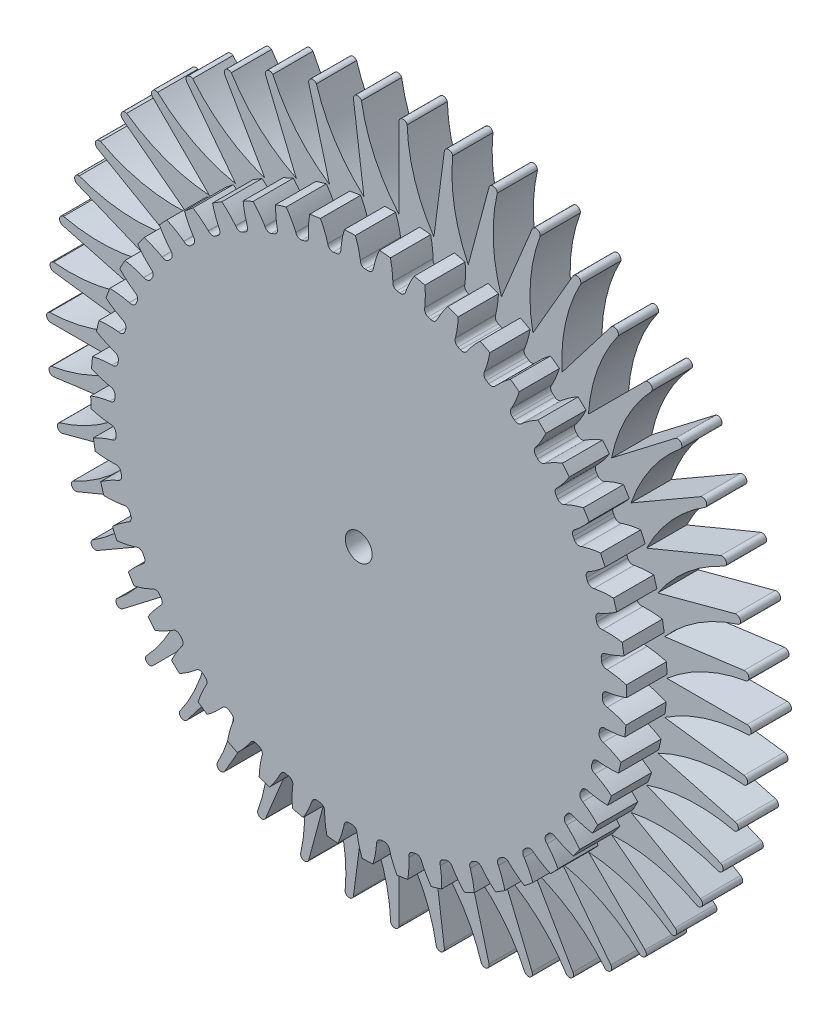
SolidWorks part; units mm, degrees
ref_plane "Front" through (0, 0, 0) normal (0, 0, 1) x (1, 0, 0)
ref_plane "Top" through (0, 0, 0) normal (0, 1, 0) x (1, 0, 0)
ref_plane "Right" through (0, 0, 0) normal (1, 0, 0) x (0, 0, -1)
sketch "Sketch1" plane through (0, 0, 0) normal (0, 0, 1) x (1, 0, 0)
  line L0 (-609.6, 0) -> (609.6, 0) construction
  circle A0 centre (0, 0) radius 31.75
  circle A1 centre (0, 0) radius 30.48 construction
  circle A3 centre (0, 0) radius 28.8925 construction
  dimension "D3" = 1.27
  dimension "D1" = 2.8575
extrude "Boss-Extrude1" add sketch "Sketch1" against normal blind 4.7625
sketch "Sketch3" plane through (0, 0, 0) normal (0, 0, 1) x (1, 0, 0)
  line L0 (0, 0) -> (0, 31.75) construction
  line L1 (-7.3885, 28.5692) -> (0, 30.48)
  line L2 (-9.5921, 30.48) -> (9.5921, 30.48) construction
  line L3 (-9.2865, 28.0783) -> (9.2865, 32.8817) construction
  line L4 (-7.3885, 28.5692) -> (0, 0) construction
  line L5 (-18.8456, 22.7076) -> (0, 0) construction
  line L6 (-18.8456, 22.7076) -> (-3.0091, 35.8506) construction
  line L7 (-5.1519, 29.0559) -> (0, 0) construction
  line L8 (-5.1519, 29.0559) -> (0.1081, 29.9886) construction
  arc A0 (-7.3885, 28.5692) -> (-18.8456, 22.7076) centre (0, 0) ccw
  circle A1 centre (0, 0) radius 30.48 construction
  circle A2 centre (0, 0) radius 29.5091 construction
  arc A3 (-7.3885, 28.5692) -> (-5.1519, 29.0559) centre (0, 0) cw
  circle A4 centre (0, 0) radius 31.75 construction
  point P6 (0, 30.48)
  dimension "D1" = 7.6316
  dimension "Pressure Angle" = 14.5
  dimension "D2" = 12.9737
  dimension "D3" = 20.5799
  dimension "D4" = 2.2895
  dimension "D5" = 5.3421
sketch "Sketch4" plane through (0, 0, 0) normal (0, 0, 1) x (1, 0, 0)
  line L0 (0, 0) -> (0.9967, 30.4474) construction
  line L1 (0.192, 29.5085) -> (0.192, 28.8919)
  line L2 (0, 30.48) -> (1.9935, 30.4147) construction
  line L3 (1.7384, 29.4579) -> (1.698, 28.8426)
  line L4 (0.192, 28.8919) -> (0, 0) construction
  line L5 (0, 0) -> (0, 31.75) construction
  line L6 (-18.8456, 22.7076) -> (-3.0091, 35.8506) construction
  line L7 (-18.8456, 22.7076) -> (-3.0091, 35.8506) construction
  arc A0 (1.698, 28.8426) -> (0.192, 28.8919) centre (0, 0) ccw
  arc A1 (0, 30.48) -> (1.9935, 30.4147) centre (0, 0) cw construction
  circle A2 centre (0, 0) radius 30.48 construction
  circle A3 centre (0, 0) radius 29.5091 construction
  circle A4 centre (0, 0) radius 28.8925 construction
  arc A5 (5.3474, 35.577) -> (-3.0091, 35.8506) centre (0, 0) ccw
  spline S0 degree 2 poles (-3.0091, 35.8506) (-0.3489, 33.0435) (0.192, 29.5085) knots 0 0 0 1 1 1
  spline S1 degree 2 poles (5.3474, 35.577) (2.5093, 32.95) (1.7384, 29.4579) knots 0 0 0 1 1 1
  dimension "D1" = 1.9949
extrude "Cut-Extrude1" cut sketch "Sketch4" against normal through all
fillet "Fillet1" radius 0.5985 2 edges at (1.698, 28.8426, -2.3813) (0.192, 28.8919, -2.3813)
pattern_circular "CirPattern1" count 48 over 360 about axis through (0, 0, -4.7625) along (0, 0, 1) of "Cut-Extrude1", "Fillet1"
sketch "Sketch5" plane through (0, 0, 0) normal (0, 0, 1) x (1, 0, 0)
  line L0 (0, 2.7788) -> (0, 0) construction
  line L1 (-1.1906, 1.05) -> (1.1906, 1.05) construction
  line L2 (-1.1906, 1.05) -> (-1.1906, 2.7788) construction
  line L3 (-1.1906, 2.7788) -> (1.1906, 2.7788) construction
  line L4 (1.1906, 1.05) -> (1.1906, 2.7788) construction
  line L5 (-1.1906, 1.05) -> (1.1906, 2.7788) construction
  line L6 (-1.1906, 2.7788) -> (1.1906, 1.05) construction
  circle A0 centre (0, 0) radius 1.5875
  point P3 (0, 1.9144)
  point P8 (0, 1.5875)
  point P9 (0, -1.5875)
  dimension "Bore Min" = 3.175
  dimension "Keyway Wd" = 2.3813
  dimension "Keyway Dpt." = 1.1913
extrude "Cut-Extrude2" cut sketch "Sketch5" against normal through all
sketch "Pitch Dia" plane through (0, 0, 0) normal (0, 0, 1) x (1, 0, 0)
  circle A0 centre (0, 0) radius 30.48 construction
  circle A1 centre (0, 0) radius 30.48 construction
sketch "Sketch6" plane through (0, 0, -4.7625) normal (0, 0, -1) x (-1, 0, 0)
  line L0 (8.2175, 30.6681) -> (10.6742, 39.8367)
  line L98 (12.1502, 29.3332) -> (15.7826, 38.1026)
  line L195 (4.1442, 31.4784) -> (5.3832, 40.8892)
  line L196 (15.875, 27.4963) -> (20.621, 35.7166)
  line L291 (0, 0) -> (0, 1.5875)
  line L292 (19.3282, 25.189) -> (25.1065, 32.7195)
  line L293 (22.4506, 22.4506) -> (29.1625, 29.1625)
  line L294 (25.189, 19.3282) -> (32.7195, 25.1065)
  line L295 (27.4963, 15.875) -> (35.7166, 20.621)
  line L296 (29.3332, 12.1502) -> (38.1026, 15.7826)
  line L297 (30.6681, 8.2175) -> (39.8367, 10.6742)
  line L298 (31.4784, 4.1442) -> (40.8892, 5.3832)
  line L299 (31.75, 0) -> (41.242, 0)
  line L300 (31.4784, -4.1442) -> (40.8892, -5.3832)
  line L301 (30.6681, -8.2175) -> (39.8367, -10.6742)
  line L302 (29.3332, -12.1502) -> (38.1026, -15.7826)
  line L303 (27.4963, -15.875) -> (35.7166, -20.621)
  line L304 (25.189, -19.3282) -> (32.7195, -25.1065)
  line L305 (22.4506, -22.4506) -> (29.1625, -29.1625)
  line L306 (19.3282, -25.189) -> (25.1065, -32.7195)
  line L307 (15.875, -27.4963) -> (20.621, -35.7166)
  line L308 (12.1502, -29.3332) -> (15.7826, -38.1026)
  line L309 (8.2175, -30.6681) -> (10.6742, -39.8367)
  line L310 (4.1442, -31.4784) -> (5.3832, -40.8892)
  line L311 (0, -31.75) -> (0, -41.242)
  line L312 (-4.1442, -31.4784) -> (-5.3832, -40.8892)
  line L313 (-8.2175, -30.6681) -> (-10.6742, -39.8367)
  line L314 (-12.1502, -29.3332) -> (-15.7826, -38.1026)
  line L315 (-15.875, -27.4963) -> (-20.621, -35.7166)
  line L316 (-19.3282, -25.189) -> (-25.1065, -32.7195)
  line L317 (-22.4506, -22.4506) -> (-29.1625, -29.1625)
  line L318 (-25.189, -19.3282) -> (-32.7195, -25.1065)
  line L319 (-27.4963, -15.875) -> (-35.7166, -20.621)
  line L320 (-29.3332, -12.1502) -> (-38.1026, -15.7826)
  line L321 (-30.6681, -8.2175) -> (-39.8367, -10.6742)
  line L322 (-31.4784, -4.1442) -> (-40.8892, -5.3832)
  line L323 (-31.75, 0) -> (-41.242, 0)
  line L324 (-31.4784, 4.1442) -> (-40.8892, 5.3832)
  line L325 (-30.6681, 8.2175) -> (-39.8367, 10.6742)
  line L326 (-29.3332, 12.1502) -> (-38.1026, 15.7826)
  line L327 (-27.4963, 15.875) -> (-35.7166, 20.621)
  line L328 (-25.189, 19.3282) -> (-32.7195, 25.1065)
  line L329 (-22.4506, 22.4506) -> (-29.1625, 29.1625)
  line L330 (-19.3282, 25.189) -> (-25.1065, 32.7195)
  line L331 (-15.875, 27.4963) -> (-20.621, 35.7166)
  line L332 (-12.1502, 29.3332) -> (-15.7826, 38.1026)
  line L333 (-8.2175, 30.6681) -> (-10.6742, 39.8367)
  line L334 (-4.1442, 31.4784) -> (-5.3832, 40.8892)
  line L335 (0, 31.75) -> (0, 41.242)
  arc A98 (5.3832, 40.8892) -> (4.4351, 41.1675) centre (4.8874, 40.9544) ccw
  circle A146 centre (0, 0) radius 1.5875
  arc A147 (0, 31.75) -> (4.4351, 41.1675) centre (-14.4043, 44.2867) ccw
  arc A148 (10.6742, 39.8367) -> (9.7706, 40.2364) centre (10.1913, 39.9661) ccw
  arc A149 (4.1442, 31.4784) -> (9.7706, 40.2364) centre (-8.5005, 45.7879) ccw
  arc A150 (15.7826, 38.1026) -> (14.9389, 38.6168) centre (15.3207, 38.294) ccw
  arc A151 (8.2175, 30.6681) -> (14.9389, 38.6168) centre (-2.4513, 46.5058) ccw
  arc A152 (20.621, 35.7166) -> (19.8516, 36.3365) centre (20.188, 35.9666) ccw
  arc A153 (12.1502, 29.3332) -> (19.8516, 36.3365) centre (3.6399, 46.4278) ccw
  arc A154 (25.1065, 32.7195) -> (24.4246, 33.4345) centre (24.7099, 33.0239) ccw
  arc A155 (15.875, 27.4963) -> (24.4246, 33.4345) centre (9.6688, 45.5555) ccw
  arc A156 (29.1625, 29.1625) -> (28.5798, 29.9604) centre (28.8089, 29.5161) ccw
  arc A157 (19.3282, 25.189) -> (28.5798, 29.9604) centre (15.5323, 43.9038) ccw
  arc A158 (32.7195, 25.1065) -> (32.2459, 25.9737) centre (32.4151, 25.5032) ccw
  arc A159 (22.4506, 22.4506) -> (32.2459, 25.9737) centre (21.13, 41.5008) ccw
  arc A160 (35.7166, 20.621) -> (35.3603, 21.5426) centre (35.4666, 21.054) ccw
  arc A161 (25.189, 19.3282) -> (35.3603, 21.5426) centre (26.3662, 38.3877) ccw
  arc A162 (38.1026, 15.7826) -> (37.8696, 16.7428) centre (37.9113, 16.2446) ccw
  arc A163 (27.4963, 15.875) -> (37.8696, 16.7428) centre (31.1512, 34.6178) ccw
  arc A164 (39.8367, 10.6742) -> (39.731, 11.6566) centre (39.7073, 11.1572) ccw
  arc A165 (29.3332, 12.1502) -> (39.731, 11.6566) centre (35.4033, 30.2556) ccw
  arc A166 (40.8892, 5.3832) -> (40.9126, 6.371) centre (40.8239, 5.8789) ccw
  arc A167 (30.6681, 8.2175) -> (40.9126, 6.371) centre (39.0495, 25.3757) ccw
  arc A168 (41.242, 0) -> (41.3942, 0.9763) centre (41.242, 0.5) ccw
  arc A169 (31.4784, 4.1442) -> (41.3942, 0.9763) centre (42.0277, 20.0616) ccw
  arc A170 (40.8892, -5.3832) -> (41.1675, -4.4351) centre (40.9544, -4.8874) ccw
  arc A171 (31.75, 0) -> (41.1675, -4.4351) centre (44.2867, 14.4043) ccw
  arc A172 (39.8367, -10.6742) -> (40.2364, -9.7706) centre (39.9661, -10.1913) ccw
  arc A173 (31.4784, -4.1442) -> (40.2364, -9.7706) centre (45.7879, 8.5005) ccw
  arc A174 (38.1026, -15.7826) -> (38.6168, -14.9389) centre (38.294, -15.3207) ccw
  arc A175 (30.6681, -8.2175) -> (38.6168, -14.9389) centre (46.5058, 2.4513) ccw
  arc A176 (35.7166, -20.621) -> (36.3365, -19.8516) centre (35.9666, -20.188) ccw
  arc A177 (29.3332, -12.1502) -> (36.3365, -19.8516) centre (46.4278, -3.6399) ccw
  arc A178 (32.7195, -25.1065) -> (33.4345, -24.4246) centre (33.0239, -24.7099) ccw
  arc A179 (27.4963, -15.875) -> (33.4345, -24.4246) centre (45.5555, -9.6688) ccw
  arc A180 (29.1625, -29.1625) -> (29.9604, -28.5798) centre (29.5161, -28.8089) ccw
  arc A181 (25.189, -19.3282) -> (29.9604, -28.5798) centre (43.9038, -15.5323) ccw
  arc A182 (25.1065, -32.7195) -> (25.9737, -32.2459) centre (25.5032, -32.4151) ccw
  arc A183 (22.4506, -22.4506) -> (25.9737, -32.2459) centre (41.5008, -21.13) ccw
  arc A184 (20.621, -35.7166) -> (21.5426, -35.3603) centre (21.054, -35.4666) ccw
  arc A185 (19.3282, -25.189) -> (21.5426, -35.3603) centre (38.3877, -26.3662) ccw
  arc A186 (15.7826, -38.1026) -> (16.7428, -37.8696) centre (16.2446, -37.9113) ccw
  arc A187 (15.875, -27.4963) -> (16.7428, -37.8696) centre (34.6178, -31.1512) ccw
  arc A188 (10.6742, -39.8367) -> (11.6566, -39.731) centre (11.1572, -39.7073) ccw
  arc A189 (12.1502, -29.3332) -> (11.6566, -39.731) centre (30.2556, -35.4033) ccw
  arc A190 (5.3832, -40.8892) -> (6.371, -40.9126) centre (5.8789, -40.8239) ccw
  arc A191 (8.2175, -30.6681) -> (6.371, -40.9126) centre (25.3757, -39.0495) ccw
  arc A192 (0, -41.242) -> (0.9763, -41.3942) centre (0.5, -41.242) ccw
  arc A193 (4.1442, -31.4784) -> (0.9763, -41.3942) centre (20.0616, -42.0277) ccw
  arc A194 (-5.3832, -40.8892) -> (-4.4351, -41.1675) centre (-4.8874, -40.9544) ccw
  arc A195 (0, -31.75) -> (-4.4351, -41.1675) centre (14.4043, -44.2867) ccw
  arc A196 (-10.6742, -39.8367) -> (-9.7706, -40.2364) centre (-10.1913, -39.9661) ccw
  arc A197 (-4.1442, -31.4784) -> (-9.7706, -40.2364) centre (8.5005, -45.7879) ccw
  arc A198 (-15.7826, -38.1026) -> (-14.9389, -38.6168) centre (-15.3207, -38.294) ccw
  arc A199 (-8.2175, -30.6681) -> (-14.9389, -38.6168) centre (2.4513, -46.5058) ccw
  arc A200 (-20.621, -35.7166) -> (-19.8516, -36.3365) centre (-20.188, -35.9666) ccw
  arc A201 (-12.1502, -29.3332) -> (-19.8516, -36.3365) centre (-3.6399, -46.4278) ccw
  arc A202 (-25.1065, -32.7195) -> (-24.4246, -33.4345) centre (-24.7099, -33.0239) ccw
  arc A203 (-15.875, -27.4963) -> (-24.4246, -33.4345) centre (-9.6688, -45.5555) ccw
  arc A204 (-29.1625, -29.1625) -> (-28.5798, -29.9604) centre (-28.8089, -29.5161) ccw
  arc A205 (-19.3282, -25.189) -> (-28.5798, -29.9604) centre (-15.5323, -43.9038) ccw
  arc A206 (-32.7195, -25.1065) -> (-32.2459, -25.9737) centre (-32.4151, -25.5032) ccw
  arc A207 (-22.4506, -22.4506) -> (-32.2459, -25.9737) centre (-21.13, -41.5008) ccw
  arc A208 (-35.7166, -20.621) -> (-35.3603, -21.5426) centre (-35.4666, -21.054) ccw
  arc A209 (-25.189, -19.3282) -> (-35.3603, -21.5426) centre (-26.3662, -38.3877) ccw
  arc A210 (-38.1026, -15.7826) -> (-37.8696, -16.7428) centre (-37.9113, -16.2446) ccw
  arc A211 (-27.4963, -15.875) -> (-37.8696, -16.7428) centre (-31.1512, -34.6178) ccw
  arc A212 (-39.8367, -10.6742) -> (-39.731, -11.6566) centre (-39.7073, -11.1572) ccw
  arc A213 (-29.3332, -12.1502) -> (-39.731, -11.6566) centre (-35.4033, -30.2556) ccw
  arc A214 (-40.8892, -5.3832) -> (-40.9126, -6.371) centre (-40.8239, -5.8789) ccw
  arc A215 (-30.6681, -8.2175) -> (-40.9126, -6.371) centre (-39.0495, -25.3757) ccw
  arc A216 (-41.242, 0) -> (-41.3942, -0.9763) centre (-41.242, -0.5) ccw
  arc A217 (-31.4784, -4.1442) -> (-41.3942, -0.9763) centre (-42.0277, -20.0616) ccw
  arc A218 (-40.8892, 5.3832) -> (-41.1675, 4.4351) centre (-40.9544, 4.8874) ccw
  arc A219 (-31.75, 0) -> (-41.1675, 4.4351) centre (-44.2867, -14.4043) ccw
  arc A220 (-39.8367, 10.6742) -> (-40.2364, 9.7706) centre (-39.9661, 10.1913) ccw
  arc A221 (-31.4784, 4.1442) -> (-40.2364, 9.7706) centre (-45.7879, -8.5005) ccw
  arc A222 (-38.1026, 15.7826) -> (-38.6168, 14.9389) centre (-38.294, 15.3207) ccw
  arc A223 (-30.6681, 8.2175) -> (-38.6168, 14.9389) centre (-46.5058, -2.4513) ccw
  arc A224 (-35.7166, 20.621) -> (-36.3365, 19.8516) centre (-35.9666, 20.188) ccw
  arc A225 (-29.3332, 12.1502) -> (-36.3365, 19.8516) centre (-46.4278, 3.6399) ccw
  arc A226 (-32.7195, 25.1065) -> (-33.4345, 24.4246) centre (-33.0239, 24.7099) ccw
  arc A227 (-27.4963, 15.875) -> (-33.4345, 24.4246) centre (-45.5555, 9.6688) ccw
  arc A228 (-29.1625, 29.1625) -> (-29.9604, 28.5798) centre (-29.5161, 28.8089) ccw
  arc A229 (-25.189, 19.3282) -> (-29.9604, 28.5798) centre (-43.9038, 15.5323) ccw
  arc A230 (-25.1065, 32.7195) -> (-25.9737, 32.2459) centre (-25.5032, 32.4151) ccw
  arc A231 (-22.4506, 22.4506) -> (-25.9737, 32.2459) centre (-41.5008, 21.13) ccw
  arc A232 (-20.621, 35.7166) -> (-21.5426, 35.3603) centre (-21.054, 35.4666) ccw
  arc A233 (-19.3282, 25.189) -> (-21.5426, 35.3603) centre (-38.3877, 26.3662) ccw
  arc A234 (-15.7826, 38.1026) -> (-16.7428, 37.8696) centre (-16.2446, 37.9113) ccw
  arc A235 (-15.875, 27.4963) -> (-16.7428, 37.8696) centre (-34.6178, 31.1512) ccw
  arc A236 (-10.6742, 39.8367) -> (-11.6566, 39.731) centre (-11.1572, 39.7073) ccw
  arc A237 (-12.1502, 29.3332) -> (-11.6566, 39.731) centre (-30.2556, 35.4033) ccw
  arc A238 (-5.3832, 40.8892) -> (-6.371, 40.9126) centre (-5.8789, 40.8239) ccw
  arc A239 (-8.2175, 30.6681) -> (-6.371, 40.9126) centre (-25.3757, 39.0495) ccw
  arc A240 (0, 41.242) -> (-0.9763, 41.3942) centre (-0.5, 41.242) ccw
  arc A241 (-4.1442, 31.4784) -> (-0.9763, 41.3942) centre (-20.0616, 42.0277) ccw
  point P293 (0, 0)
extrude "Boss-Extrude3" add sketch "Sketch6" along normal blind 4.7625 contours A204 A194 region at (-13.0318, 33.4133, -4.7625)
equation "\"D1@Sketch4\" = 1.5708/(\"Number of Teeth@Sketch1\"/\"Ptich Dia@Sketch1\")"
equation "\"D1@CirPattern1\" = \"Number of Teeth@Sketch1\""
equation "\"D1@Fillet1\" = \"D1@Sketch4\"*.3"
equation "\"D1@Sketch1\" = 2.250/(\"Number of Teeth@Sketch1\"/\"Ptich Dia@Sketch1\")"
